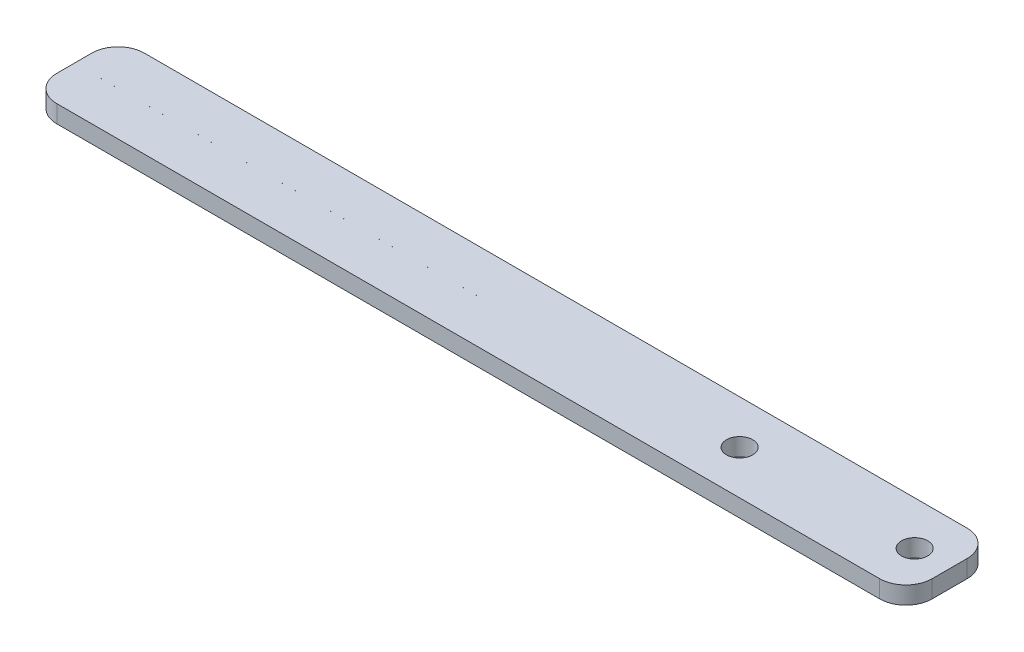
SolidWorks part; units mm, degrees
ref_plane "Front Plane" through (0, 0, 0) normal (0, 0, 1) x (1, 0, 0)
ref_plane "Top Plane" through (0, 0, 0) normal (0, 1, 0) x (1, 0, 0)
ref_plane "Right Plane" through (0, 0, 0) normal (1, 0, 0) x (0, 0, -1)
sketch "Sketch1" plane through (0, 0, 0) normal (0, 1, 0) x (1, 0, 0)
  line L1 (-50, 5) -> (50, 5)
  line L2 (-50, 5) -> (-50, -5)
  line L3 (-50, -5) -> (50, -5)
  line L4 (50, 5) -> (50, -5)
  line L5 (-50, 5) -> (50, -5) construction
  line L6 (-50, -5) -> (50, 5) construction
  point P0 (0, 0)
  dimension "D1" = 10
  dimension "D2" = 100
extrude "Boss-Extrude1" add sketch "Sketch1" along normal blind 2
sketch "Sketch2" plane through (0, 2, 0) normal (0, 1, 0) x (1, 0, 0)
  line L0 (26.3156, 5) -> (26.3156, -5) construction
  line L1 (-50, -5) -> (50, -5) construction
  line L2 (-50, 5) -> (-50, -5) construction
  line L4 (-3, 0.0005) -> (-50, 0.0005)
  line L5 (-3, 0.0005) -> (-3, -0.0005)
  line L6 (-3, -0.0005) -> (-50, -0.0005)
  line L7 (-50, 0.0005) -> (-50, -0.0005)
  line L8 (-3, 0.0005) -> (-50, -0.0005) construction
  line L9 (-3, -0.0005) -> (-50, 0.0005) construction
  point P0 (-26.5, 0)
  point P10 (26.3156, 0)
  point P14 (-50, 0)
  dimension "D1" = 47
  dimension "D2" = 0.001
fillet "Fillet1" radius 3 4 edges at (50, 1, 5) (50, 1, -5) (-50, 1, -5) (-50, 1, 5)
hole_wizard "Ø3.0mm Dowel Hole1" positions "Sketch3" profile "Sketch5" hole size "Ø3.0" standard "ISO" end condition through all
sketch "Sketch3" plane through (0, 2, 0) normal (0, 1, 0) x (1, 0, 0)
  line L0 (50, -2) -> (50, 2) construction
  point P0 (46, 0)
  point P5 (26, 0)
  dimension "D1" = 20
  dimension "D2" = 4
sketch "Sketch5" plane through (46, 2, 0) normal (1, 0, 0) x (0, 0, 1)
  line L0 (0, 0) -> (0, 2)
  line L1 (0, 2) -> (1.5, 2)
  line L2 (1.5, 2) -> (1.5, 0)
  line L5 (1.5, 0) -> (0, 0)
  line L11 (0, -22.0399) -> (0, 107.95) construction
  dimension "Thru Hole Dia." = 3
  dimension "Thru Hole Depth" = 2
extrude "Cut-Extrude1" cut sketch "Sketch2" against normal blind 10
